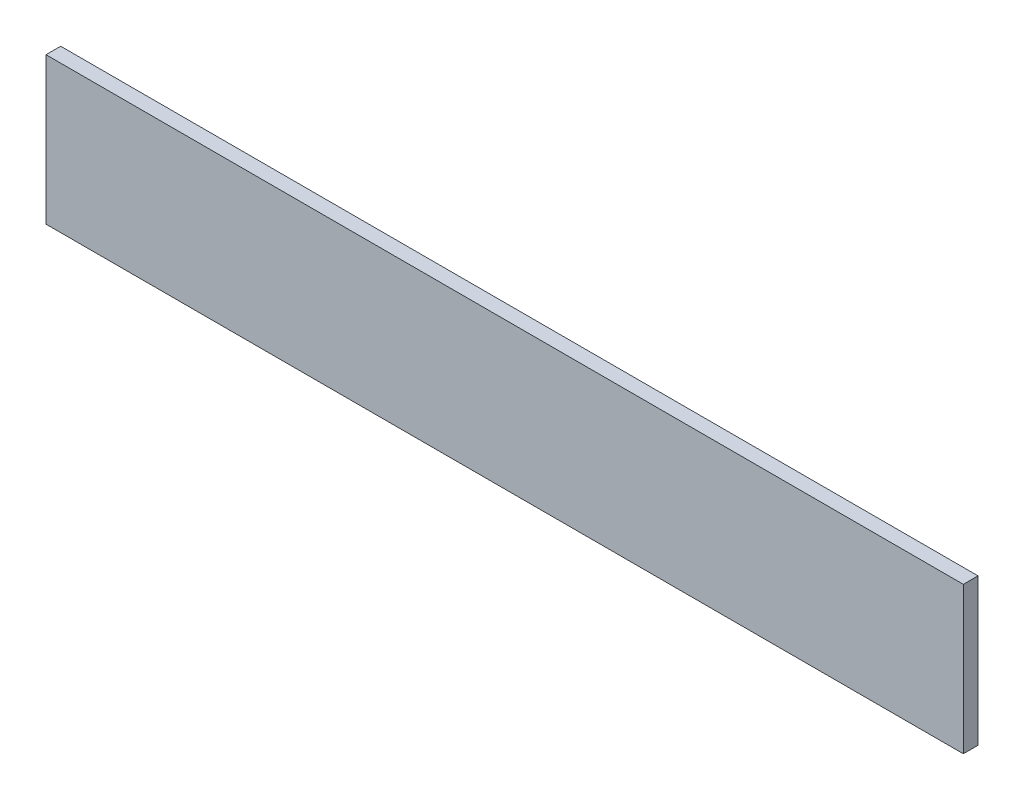
SolidWorks part; units mm, degrees
material "Pine"
ref_plane "Front Plane" through (0, 0, 0) normal (0, 0, 1) x (1, 0, 0)
ref_plane "Top Plane" through (0, 0, 0) normal (0, 1, 0) x (1, 0, 0)
ref_plane "Right Plane" through (0, 0, 0) normal (1, 0, 0) x (0, 0, -1)
sketch "Sketch1" plane through (0, 0, 0) normal (0, 0, 1) x (1, 0, 0)
  line L1 (-250, -40) -> (250, -40)
  line L2 (-250, -40) -> (-250, 40)
  line L3 (-250, 40) -> (250, 40)
  line L4 (250, -40) -> (250, 40)
  line L5 (-250, -40) -> (250, 40) construction
  line L6 (-250, 40) -> (250, -40) construction
  point P0 (0, 0)
  dimension "D1" = 500
  dimension "D2" = 80
extrude "Boss-Extrude1" add sketch "Sketch1" along normal blind 8
sketch "Sketch3" plane through (0, 0, 8) normal (0, 0, 1) x (1, 0, 0)
  line L0 (-250, 0) -> (250, 0) construction
  line L1 (-250, 40) -> (-250, -40) construction
  line L2 (250, -40) -> (250, 40) construction
  line L3 (0, 40) -> (0, -40) construction
  line L4 (250, 40) -> (-250, 40) construction
  line L5 (-250, -40) -> (250, -40) construction
  circle A0 centre (0, 0) radius 4
  circle A2 centre (-140, 0) radius 4
  circle A5 centre (140, 0) radius 4
  dimension "D1" = 8
  dimension "D3" = 8
  dimension "D6" = 140
